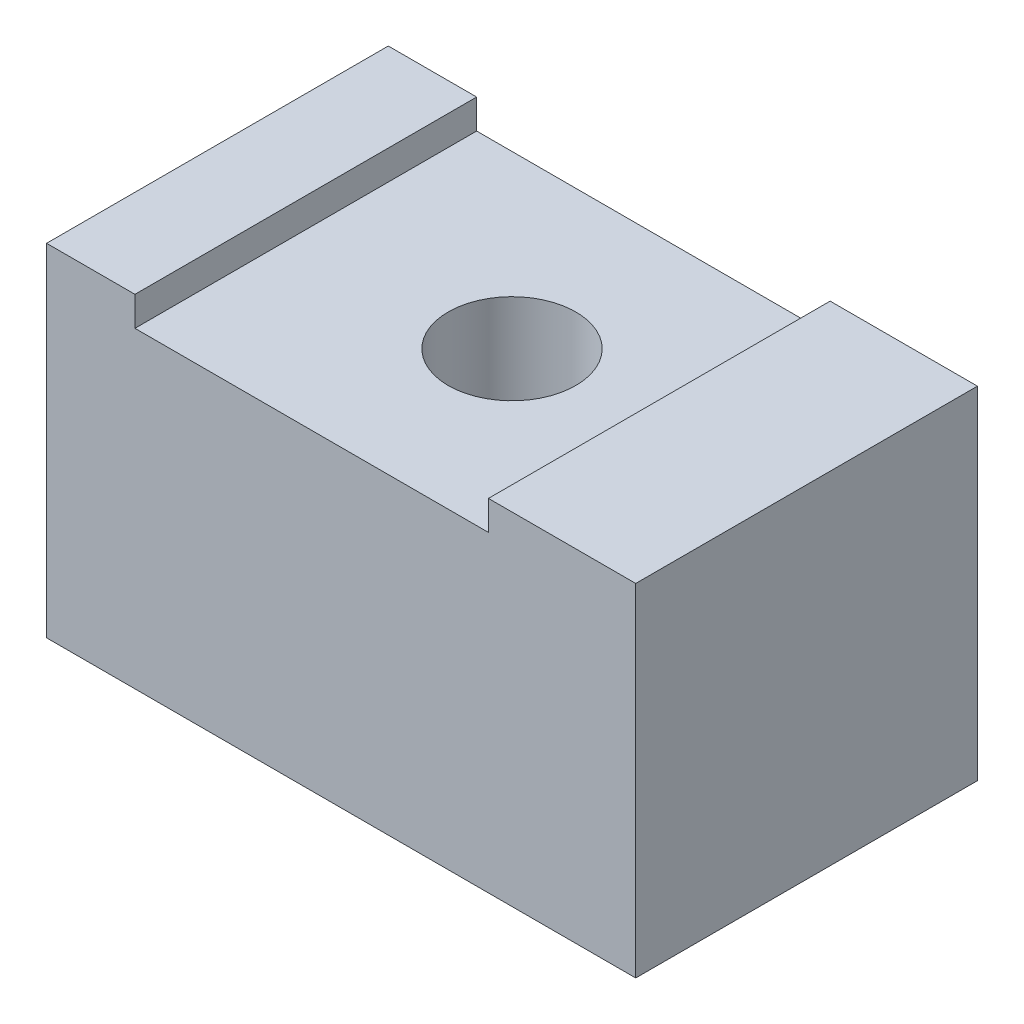
SolidWorks part; units mm, degrees
ref_plane "Front Plane" through (0, 0, 0) normal (0, 0, 1) x (1, 0, 0)
ref_plane "Top Plane" through (0, 0, 0) normal (0, 1, 0) x (1, 0, 0)
ref_plane "Right Plane" through (0, 0, 0) normal (1, 0, 0) x (0, 0, -1)
sketch "Sketch1" plane through (0, 0, 0) normal (1, 0, 0) x (0, 0, -1)
  line L1 (-7.366, 7.366) -> (7.366, 7.366)
  line L2 (-7.366, 7.366) -> (-7.366, -7.366)
  line L3 (-7.366, -7.366) -> (7.366, -7.366)
  line L4 (7.366, 7.366) -> (7.366, -7.366)
  line L5 (-7.366, 7.366) -> (7.366, -7.366) construction
  line L6 (-7.366, -7.366) -> (7.366, 7.366) construction
  point P0 (0, 0)
  dimension "D1" = 14.732
  dimension "D2" = 14.732
extrude "Boss-Extrude1" add sketch "Sketch1" along normal blind 25.4
sketch "Sketch2" plane through (0, 7.366, 0) normal (0, 1, 0) x (1, 0, 0)
  line L0 (0, 7.366) -> (0, -7.366) construction
  circle A0 centre (12.7, 0) radius 2.75
  point P6 (0, 0)
  dimension "D1" = 5.5
  dimension "D2" = 12.7
extrude "Cut-Extrude1" cut sketch "Sketch2" against normal through all
sketch "Sketch3" plane through (0, 0, -7.366) normal (0, 0, -1) x (-1, 0, 0)
  line L0 (0, -7.366) -> (0, 7.366) construction
  line L1 (0, 3.366) -> (-10, 3.366)
  line L2 (0, 3.366) -> (0, -3.492)
  line L3 (0, -3.492) -> (-10, -3.492)
  line L4 (-10, 3.366) -> (-10, -3.492)
  line L5 (-10, -0.063) -> (-4.92, -0.063) construction
  line L6 (-25.4, 7.366) -> (0, 7.366) construction
  circle A0 centre (-4.92, -0.063) radius 1.5875
  dimension "D2" = 3.175
  dimension "D1" = 6.858
  dimension "D3" = 5.08
  dimension "D4" = 10
  dimension "D5" = 4
extrude "Cut-Extrude2" cut sketch "Sketch3" against normal blind 1.778
fillet "Fillet1" radius 0.7937 2 edges at (10, 3.366, -6.477) (10, -3.492, -6.477)
sketch "Sketch5" plane through (0, 0, -7.366) normal (0, 0, -1) x (-1, 0, 0)
  line L0 (0, -7.366) -> (0, -3.492)
  line L1 (0, -7.366) -> (-3.9016, -7.366)
  line L2 (-25.4, -7.366) -> (0, -7.366) construction
sketch "Sketch6" plane through (0, 7.366, 0) normal (0, 1, 0) x (1, 0, 0)
  text T0 "Top"
sketch "Sketch7" plane through (0, 7.366, 0) normal (0, 1, 0) x (1, 0, 0)
  line L0 (25.4, 7.366) -> (0, 7.366) construction
  line L1 (3.81, 7.366) -> (19.05, 7.366)
  line L2 (3.81, 7.366) -> (3.81, -7.366)
  line L3 (3.81, -7.366) -> (19.05, -7.366)
  line L4 (19.05, 7.366) -> (19.05, -7.366)
  line L5 (25.4, -7.366) -> (0, -7.366) construction
  line L6 (25.4, 7.366) -> (25.4, -7.366) construction
  line L7 (0, 7.366) -> (0, -7.366) construction
  dimension "D1" = 6.35
  dimension "D2" = 3.81
extrude "Cut-Extrude3" cut sketch "Sketch7" against normal blind 1.27
